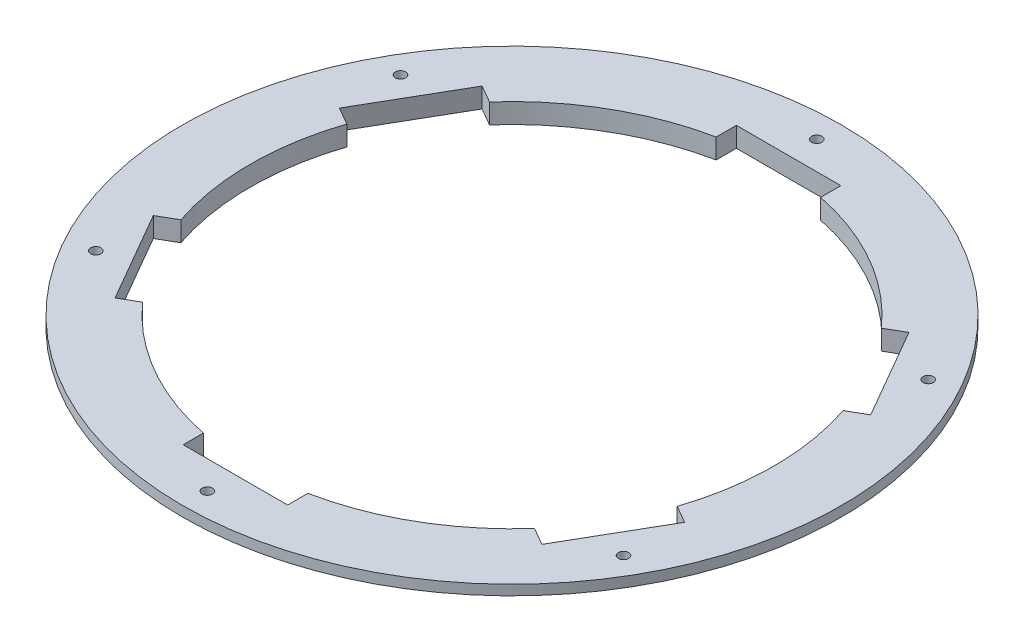
SolidWorks part; units mm, degrees
material "6061 Alloy"
ref_plane "Front Plane" through (0, 0, 0) normal (0, 0, 1) x (1, 0, 0)
ref_plane "Top Plane" through (0, 0, 0) normal (0, 1, 0) x (1, 0, 0)
ref_plane "Right Plane" through (0, 0, 0) normal (1, 0, 0) x (0, 0, -1)
sketch "Sketch1" plane through (0, 0, 0) normal (0, 1, 0) x (1, 0, 0)
  line L0 (-13.335, -65.4575) -> (-13.335, -69.3414)
  line L1 (13.335, -65.4575) -> (13.335, -69.3414)
  line L2 (-13.335, -70.612) -> (13.335, -70.612)
  line L3 (13.335, -69.3414) -> (13.335, -70.612)
  line L4 (-13.335, -69.3414) -> (-13.335, -70.612)
  circle A0 centre (0, 0) radius 66.802
  circle A1 centre (0, 0) radius 84.1375
  circle A2 centre (0, 0) radius 70.612
  circle A3 centre (0, -77.7875) radius 1.3208
  dimension "D1" = 133.604
  dimension "D2" = 168.275
  dimension "D8" = 2.6416
  dimension "D4" = 13.335
  dimension "D5" = 13.335
  dimension "D7" = 77.7875
  dimension "D3" = 3.81
extrude "Boss-Extrude1" add sketch "Sketch1" along normal blind 5.08 contours L1 A2 L0 A0 | A1 A2 A0 region at (-15.3232, 0, 67.3995) region at (-81.7577, 0, 0)
pattern_circular "CirPattern1" count 6 over 360 about axis through (0, 5.08, 0) along (0, 1, 0) of face at (-13.335, 2.54, 68.0348) of face at (13.335, 2.54, 68.0348) of face at (0, 5.08, 79.1083) of face at (0, 2.54, 70.612)
sketch "Sketch2" plane through (0, 0, 0) normal (1, 0, 0) x (0, 0, -1)
  line L0 (84.1375, 5.08) -> (-84.1375, 5.08) construction
  line L1 (-84.1375, 0) -> (84.1375, 0) construction
  line L2 (84.1375, 5.08) -> (-84.1375, 5.08)
  line L3 (-84.1375, 0) -> (84.1375, 0)
  line L4 (0, 0) -> (0, 5.08) construction
  circle A0 centre (-83.2231, 0) radius 2.667
  dimension "D1" = 5.334
  dimension "D2" = 0.9144
revolve "Cut-Revolve1" cut sketch "Sketch2" angle 360 about L4 region at (0, 0, 85.8147)
sketch "Sketch4" plane through (0, 0, 0) normal (0, -1, 0) x (1, 0, 0)
  line L0 (0, 0) -> (36.9888, -64.0664) construction
  line L1 (0, 0) -> (0, -39.7137) construction
  circle A0 centre (36.9888, -64.0664) radius 5.588
  circle M34 centre (0, 0) radius 80.5561
  dimension "D2" = 11.176
  dimension "D1" = 73.9775
  dimension "D3" = 30
extrude "Cut-Extrude1" cut sketch "Sketch4" against normal blind 1.905 contours A0 M34 region at (36.9888, 0, -64.0664)
pattern_circular "CirPattern2" count 3 over 360 about axis through (0, 0, 0) along (0, 1, 0) of "Cut-Extrude1"
equation "\"Middle Coupler Inner Daimeter\"= 4.75in"
equation "\"Middle Coupler  Wall Thickness\" = 0.25in"
equation "\"Middle Coupler Bottom Thickness\"= 0.2in"
equation "\"Bearing Rail Offset\"= 0.45in"
equation "\"3-56 UNF Tap\"= 0.089in"
equation "\"3-56 UNF Clearance\"= 0.104in"
equation "\"Ball Bearing Distance\"= 0.03in"
equation "\"D1@Sketch1\"=\"Middle Coupler Inner Daimeter\"+0.5+0.005*2in"
equation "\"TCA Outer Diameter\" = 6.625in"
equation "\"D2@Sketch1\"=\"TCA Outer Diameter\""
equation "\"D4@Sketch1\"=0.50 + (0.05/2)"
equation "\"D5@Sketch1\"=\"D4@Sketch1\""
equation "\"D7@Sketch1\"=(\"D2@Sketch1\"-0.5)/2"
equation "\"D8@Sketch1\"=\"3-56 UNF Clearance\""
equation "\"D2@Sketch2\"=\"Interstage Aeroframe Wall Thickness\"/2"
equation "\"Interstage Aeroframe Wall Thickness\" = 0.072in"
equation "\"D1@Sketch4\"=((\"Middle Coupler Inner Daimeter\"+0.625in)/2in+0.225in)"
equation "\"Compression Spring OD\"= 0.42in"
equation "\"10-24 Tap\"= 0.157in"
equation "\"10-24 Clearance\"= 0.196in"
equation "\"D2@Sketch4\"=\"Compression Spring OD\"+0.02"
equation "\"D3@Sketch1\"=0.125in+(0.05/2)"
equation "\"Lower Stage Fuselage Wall Thickness\" = 0.25in"
equation "\"6-32 Tap\" = 0.107in"
equation "\"1/4-20 Tap\" = 0.201in"
